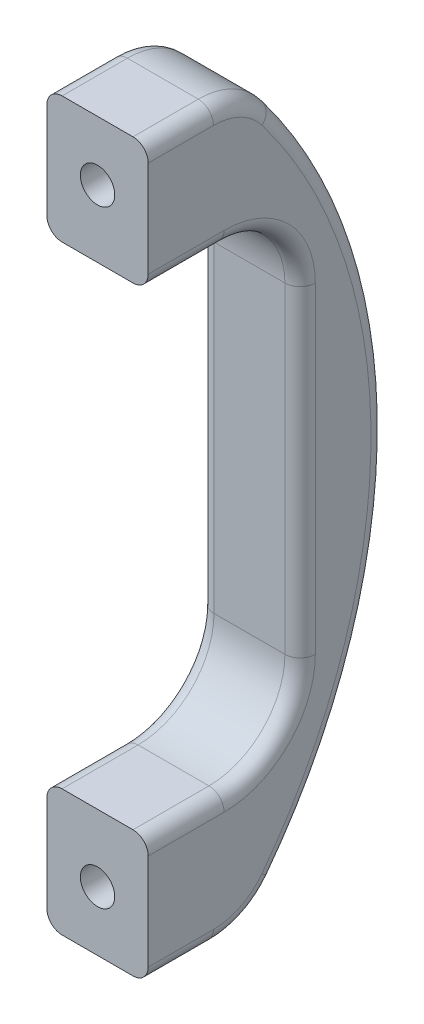
SolidWorks part; units mm, degrees
material "Custom Plastic"
ref_plane "Front Plane" through (0, 0, 0) normal (0, 0, 1) x (1, 0, 0)
ref_plane "Top Plane" through (0, 0, 0) normal (0, 1, 0) x (1, 0, 0)
ref_plane "Right Plane" through (0, 0, 0) normal (1, 0, 0) x (0, 0, -1)
sketch "Sketch1" plane through (0, 0, 0) normal (1, 0, 0) x (0, 0, -1)
  line L0 (0, 0) -> (47, 0) construction
  line L1 (0, 0) -> (0, 85.1052) construction
  line L2 (0, 71.75) -> (12.894, 71.75)
  line L3 (47, 0) -> (47, -102.7299) construction
  line L4 (30, -31.75) -> (30, 31.75)
  line L5 (15, 46.75) -> (0, 46.75)
  line L6 (0, 71.75) -> (0, 46.75)
  line L7 (0, -71.75) -> (0, -46.75)
  line L8 (15, -46.75) -> (0, -46.75)
  line L9 (0, -71.75) -> (12.894, -71.75)
  arc A0 (24.8398, -65.8218) -> (24.8398, 65.8218) centre (-61.8345, 0) ccw
  arc A1 (30, 31.75) -> (15, 46.75) centre (15, 31.75) ccw
  arc A2 (30, -31.75) -> (15, -46.75) centre (15, -31.75) cw
  arc A3 (12.894, -71.75) -> (24.8398, -65.8218) centre (12.894, -56.75) ccw
  arc A4 (12.894, 71.75) -> (24.8398, 65.8218) centre (12.894, 56.75) cw
  point P8 (30, -46.75)
  point P14 (30, 46.75)
  point P20 (30, 0)
  point P23 (20, -71.75)
  point P26 (20, 71.75)
  dimension "D1" = 47
  dimension "D6" = 15
  dimension "D7" = 15
  dimension "D2" = 71.75
  dimension "D3" = 20
  dimension "D4" = 30
  dimension "D5" = 25
extrude "Boss-Extrude1" add sketch "Sketch1" along normal mid plane 20
fillet "Fillet1" radius 3 20 edges at (-10, 46.75, -7.5) (-10, 42.3566, -25.6066) (-10, -46.75, -7.5) (-10, -42.3566, -25.6066) (10, 46.75, -7.5) (10, -46.75, -7.5) (10, -42.3566, -25.6066) (10, 0, -30) (-10, -71.75, -6.447) (-10, -70.1865, -19.5619) (-10, 0, -47) (-10, 70.1865, -19.5619) (10, -71.75, -6.447) (10, -70.1865, -19.5619) (10, 0, -47) (10, 70.1865, -19.5619) (-10, 0, -30) (10, 42.3566, -25.6066) (-10, 71.75, -6.447) (10, 71.75, -6.447)
sketch "Sketch2" plane through (0, 0, 0) normal (1, 0, 0) x (0, 0, -1)
  line L0 (-10.3944, 60) -> (52.6974, 60) construction
  line L1 (-1.8448, 63.4) -> (11, 63.4)
  line L2 (11, 63.4) -> (11, 65.75)
  line L3 (11, 65.75) -> (41, 65.75)
  line L4 (0, 68.75) -> (0, 49.75) construction
  line L5 (-1.8448, 63.4) -> (-1.8448, 60)
  line L6 (-1.8448, 60) -> (41, 60)
  line L7 (41, 60) -> (41, 65.75)
  dimension "D1" = 60
  dimension "D2" = 6.8
  dimension "D3" = 11.5
  dimension "D4" = 11
  dimension "D5" = 30
revolve "Cut-Revolve1" cut sketch "Sketch2" angle 360 about L0
mirror "Mirror1" about plane through (0, 0, 0) normal (0, 1, 0) of "Cut-Revolve1"
fillet "Fillet2" radius 1 4 edges at (3.4, 60, -11) (3.4, -60, -11) (-5.6244, -58.8047, -29.7458) (-5.5794, 61.3901, -28.0332)
